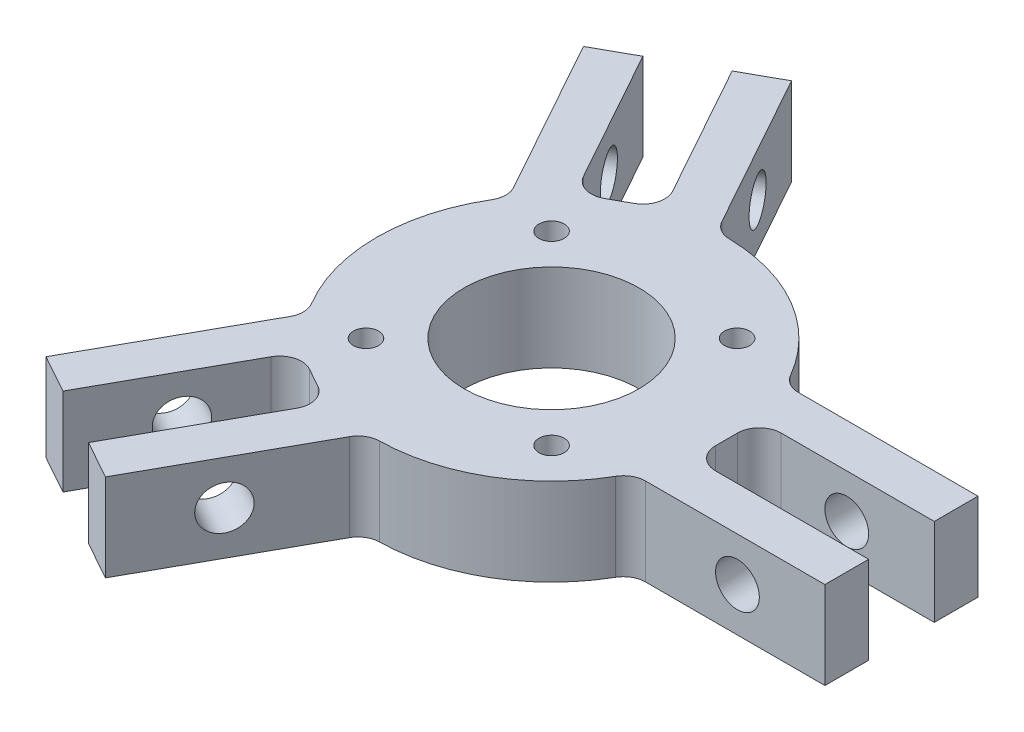
SolidWorks part; units mm, degrees
material "6061 Alloy"
ref_plane "Front Plane" through (0, 0, 0) normal (0, 0, 1) x (1, 0, 0)
ref_plane "Top Plane" through (0, 0, 0) normal (0, 1, 0) x (1, 0, 0)
ref_plane "Right Plane" through (0, 0, 0) normal (1, 0, 0) x (0, 0, -1)
sketch3d "Planning"
  line L0 (0, 0, 0) -> (38.1, 0, 0) construction
  line L1 (38.1, 0, 0) -> (355.6, -190.5, 0) construction
  line L2 (355.6, -190.5, 0) -> (355.6, -203.2, 0) construction
  line L3 (0, 0, 0) -> (-18.503, 0, 33.3054) construction
  line L4 (0, 0, 0) -> (-18.503, 0, -33.3054) construction
  line L5 (-18.503, 0, 33.3054) -> (-127, -190.5, 228.6) construction
  line L6 (-127, -190.5, 228.6) -> (-127, -203.2, 228.6) construction
  line L7 (-18.503, 0, -33.3054) -> (-127, -190.5, -228.6) construction
  line L8 (-127, -190.5, -228.6) -> (-127, -203.2, -228.6) construction
  line L9 (-18.503, 0, -33.3054) -> (-18.503, 0, 33.3054) construction
  line L10 (-127, -203.2, -228.6) -> (-127, -203.2, 228.6) construction
  line L11 (355.6, -203.2, 0) -> (-127, -203.2, 0) construction
  line L12 (0, 0, 0) -> (0, -203.2, 0) construction
  point P11 (-18.503, 0, 0)
  dimension "D1" = 38.1
  dimension "D2" = 12.7
  dimension "D3" = 203.2
  dimension "D4" = 482.6
  dimension "D5" = 127
  dimension "D6" = 457.2
sketch "Sketch1" plane through (0, 0, 0) normal (0, 1, 0) x (1, 0, 0)
  line L0 (0, 0) -> (25.4, 0) construction
  line L1 (25.4, 4.7625) -> (25.4, -4.7625)
  line L2 (25.4, -4.7625) -> (50.8, -4.7625)
  line L3 (50.8, -4.7625) -> (50.8, -11.1125)
  line L4 (25.4, 4.7625) -> (50.8, 4.7625)
  line L5 (13.4704, 13.4704) -> (-13.4704, -13.4704) construction
  line L6 (13.4704, -13.4704) -> (-13.4704, 13.4704) construction
  line L7 (50.8, 4.7625) -> (50.8, 11.1125)
  line L8 (0, 0) -> (-12.3353, -22.2036) construction
  line L9 (38.1, 4.7625) -> (38.1, -4.7625) construction
  line L10 (-34.3847, -39.0105) -> (-28.8338, -42.0943)
  line L11 (-28.8338, -42.0943) -> (-16.4985, -19.8907)
  line L12 (-16.4985, -19.8907) -> (-8.1722, -24.5165)
  line L13 (-8.1722, -24.5165) -> (-20.5075, -46.7201)
  line L14 (-20.5075, -46.7201) -> (-14.9566, -49.8039)
  line L15 (-14.9566, -49.8039) -> (-1.3781, -25.3626)
  line L16 (50.8, -11.1125) -> (22.8401, -11.1125)
  line L17 (-34.3847, -39.0105) -> (-20.8062, -14.5692)
  line L18 (0, 0) -> (-12.3353, 22.2036) construction
  line L19 (-14.9566, 49.8039) -> (-1.3781, 25.3626)
  line L20 (-20.5075, 46.7201) -> (-14.9566, 49.8039)
  line L21 (-8.1722, 24.5165) -> (-20.5075, 46.7201)
  line L22 (-16.4985, 19.8907) -> (-8.1722, 24.5165)
  line L23 (-28.8338, 42.0943) -> (-16.4985, 19.8907)
  line L24 (-34.3847, 39.0105) -> (-28.8338, 42.0943)
  line L25 (-34.3847, 39.0105) -> (-20.8062, 14.5692)
  line L26 (50.8, 11.1125) -> (22.8401, 11.1125)
  line L27 (0, 0) -> (-18.503, 33.3054) construction
  circle A0 centre (0, 0) radius 12.7
  circle A1 centre (-13.4704, 13.4704) radius 1.8288
  circle A2 centre (13.4704, 13.4704) radius 1.8288
  circle A3 centre (13.4704, -13.4704) radius 1.8288
  circle A4 centre (-13.4704, -13.4704) radius 1.8288
  arc A5 (-1.3781, -25.3626) -> (22.8401, -11.1125) centre (0, 0) ccw
  arc A6 (-1.3781, 25.3626) -> (22.8401, 11.1125) centre (0, 0) cw
  arc A7 (-20.8062, 14.5692) -> (-20.8062, -14.5692) centre (0, 0) ccw
  dimension "D3" = 25.4
  dimension "D5" = 3.6576
  dimension "D8" = 25.4
  dimension "D1" = 9.525
  dimension "D2" = 25.4
  dimension "D4" = 38.1
  dimension "D6" = 6.35
extrude "Boss-Extrude1" add sketch "Sketch1" along normal mid plane 12.7
hole_wizard "1/4 (0.25) Diameter Hole1" positions "3DSketch1" profile "Sketch4" hole size "1/4" standard "ANSI Inch" end condition up to next
sketch3d "3DSketch1"
  line L0 (25.4, -6.35, 4.7625) -> (50.8, 6.35, 4.7625) construction
  line L3 (25.4, -6.35, -4.7625) -> (50.8, 6.35, -4.7625) construction
  line L6 (-8.1722, -6.35, -24.5165) -> (-20.5075, 6.35, -46.7201) construction
  line L9 (-16.4985, -6.35, -19.8907) -> (-28.8338, 6.35, -42.0943) construction
  line L12 (-8.1722, -6.35, 24.5165) -> (-20.5075, 6.35, 46.7201) construction
  line L15 (-28.8338, 6.35, 42.0943) -> (-16.4985, -6.35, 19.8907) construction
  point P0 (38.1, 0, -4.7625)
  point P2 (-14.3398, 0, -35.6183)
  point P4 (-22.6662, 0, 30.9925)
  point P6 (-14.3398, 0, 35.6183)
  point P8 (-22.6662, 0, -30.9925)
  point P10 (38.1, 0, 4.7625)
sketch "Sketch4" plane through (38.1, 0, -4.7625) normal (1, 0, 0) x (0, -1, 0)
  line L0 (0, 0) -> (0, 6.35)
  line L1 (0, 6.35) -> (3.175, 6.35)
  line L2 (3.175, 6.35) -> (3.175, 0)
  line L5 (3.175, 0) -> (0, 0)
  line L11 (0, -6.35) -> (0, 107.95) construction
  dimension "Thru Hole Dia." = 6.35
  dimension "Thru Hole Depth" = 6.35
fillet "Fillet1" radius 3.175 12 edges at (-20.8062, 0, 14.5692) (-16.4985, 0, 19.8907) (-8.1722, 0, 24.5165) (-1.3781, 0, 25.3626) (22.8401, 0, 11.1125) (25.4, 0, -4.7625) (22.8401, 0, -11.1125) (-1.3781, 0, -25.3626) (-8.1722, 0, -24.5165) (-16.4985, 0, -19.8907) (-20.8062, 0, -14.5692) (25.4, 0, 4.7625)
